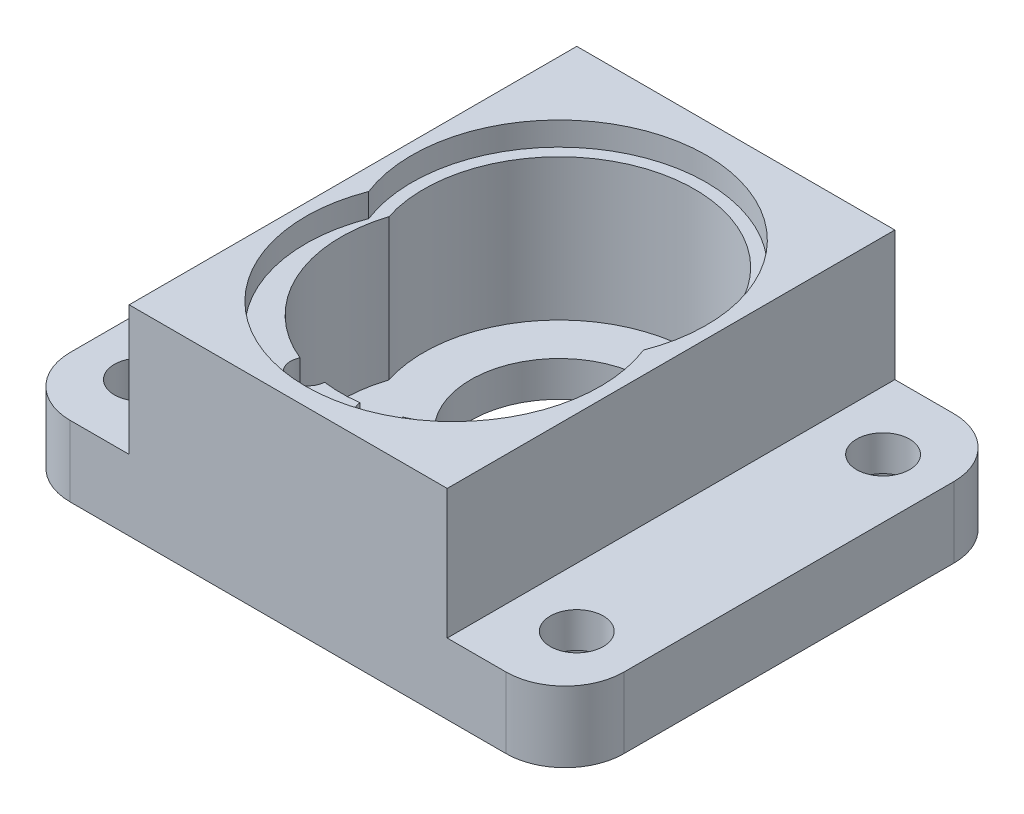
SolidWorks part; units mm, degrees
ref_plane "前视基准面" through (0, 0, 0) normal (0, 0, 1) x (1, 0, 0)
ref_plane "上视基准面" through (0, 0, 0) normal (0, 1, 0) x (1, 0, 0)
ref_plane "右视基准面" through (0, 0, 0) normal (1, 0, 0) x (0, 0, -1)
sketch "草图1" plane through (0, 0, 0) normal (0, 1, 0) x (1, 0, 0)
  line L0 (0, 0) -> (0, 23.6508) construction
  line L1 (-3, -10) -> (3, -10) construction
  line L2 (-9.5, 0) -> (9.5, 0) construction
  line L3 (0, 8.3) -> (0, -10) construction
  line L4 (0, 0) -> (10.4267, 0) construction
  line L5 (-13.5, 23.3) -> (-13.5, -14.7)
  line L6 (-13.5, 23.3) -> (13.5, 23.3)
  line L7 (0, 0.8) -> (1.4468, 0.8) construction
  line L8 (-13.5, -14.7) -> (13.5, -14.7)
  line L9 (0, -2) -> (1.3489, -2) construction
  line L10 (13.5, 23.3) -> (13.5, -14.7)
  circle A0 centre (0, 8.3) radius 7.5
  circle A1 centre (0, -5.5) radius 3.5
  circle A3 centre (-9.5, 0) radius 1.5
  circle A6 centre (-3, -10) radius 1.5
  circle A8 centre (9.5, 0) radius 1.5
  circle A9 centre (3, -10) radius 1.5
  dimension "D3" = 15
  dimension "D4" = 3
  dimension "D7" = 3
  dimension "D12" = 7
  dimension "D2" = 18.3
  dimension "D6" = 6
  dimension "D11" = 4.5
  dimension "D1" = 8.3
  dimension "D5" = 19
  dimension "D8" = 27
  dimension "D9" = 38
  dimension "D10" = 23
extrude "凸台-拉伸1" add sketch "草图1" along normal blind 3
sketch "草图4" plane through (0, 0, -23.3) normal (0, 0, -1) x (-1, 0, 0)
  line L0 (0, 0) -> (0, 15.4348) construction
  line L1 (-13.5, 0) -> (-23.5, 0)
  line L2 (-13.5, 0) -> (-13.5, 6)
  line L3 (-13.5, 6) -> (-23.5, 6)
  line L4 (-23.5, 0) -> (-23.5, 6)
  line L5 (13.5, 0) -> (23.5, 0)
  line L6 (13.5, 0) -> (13.5, 6)
  line L7 (23.5, 0) -> (23.5, 6)
  line L8 (13.5, 6) -> (23.5, 6)
  dimension "D1" = 10
  dimension "D2" = 6
extrude "凸台-拉伸3" add sketch "草图4" against normal up to surface (38 mm away) up to face at (0, 1.5, 14.7)
sketch "草图6" plane through (0, 0, 0) normal (0, -1, 0) x (1, 0, 0)
  circle A0 centre (-9.5, 0) radius 2.5
  circle A1 centre (9.5, 0) radius 2.5
  dimension "D1" = 5
  dimension "D2" = 5
extrude "切除-拉伸3" cut sketch "草图6" against normal blind 1
sketch "草图7" plane through (0, 3, 0) normal (0, 1, 0) x (1, 0, 0)
  line L0 (0, 23.3) -> (0, -14.7) construction
  line L1 (0, 0) -> (0, 24.4956) construction
  line L2 (0, 19.8) -> (8.5448, 19.8) construction
  line L3 (-10.9545, 4.8) -> (10.9545, 4.8) construction
  line L4 (0, -10.2) -> (9.1954, -10.2) construction
  line L5 (-13.5, 23.3) -> (13.5, 23.3)
  line L6 (-13.5, 23.3) -> (-13.5, -14.7)
  line L7 (-13.5, -14.7) -> (13.5, -14.7)
  line L8 (13.5, 23.3) -> (13.5, -14.7)
  line L9 (-13.5, -14.7) -> (13.5, -14.7) construction
  arc A1 (10.9545, 4.8) -> (-10.9545, 4.8) centre (0, 8.3) ccw
  arc A3 (-10.9545, 4.8) -> (10.9545, 4.8) centre (0, 1.3) ccw
  circle M1 centre (3, -10) radius 1.5
  circle M8 centre (-3, -10) radius 1.5
  dimension "D1" = 11.5
  dimension "D2" = 11.5
  dimension "D3" = 30
  dimension "D5" = 27
  dimension "D4" = 38
extrude "凸台-拉伸4" add sketch "草图7" along normal blind 14 contours A3 A1 M1 M8 region at (0, 3, -22.8338)
sketch "草图9" plane through (0, 3, 0) normal (0, 1, 0) x (1, 0, 0)
  line L0 (0, -13.2) -> (-15.6514, -13.2) construction
  line L1 (0, 20.8) -> (-29.1283, 20.8) construction
  arc A1 (11.6619, 3.8) -> (-11.6619, 3.8) centre (0, 8.3) ccw
  arc A2 (-11.6619, 3.8) -> (11.6619, 3.8) centre (0, -0.7) ccw
  dimension "D1" = 25
  dimension "D2" = 25
  dimension "D3" = 34
sketch "草图13" plane through (0, 6, 0) normal (0, 1, 0) x (1, 0, 0)
  line L0 (-18.5, 23.3) -> (-18.5, -14.7) construction
  line L1 (-23.5, 23.3) -> (-13.5, 23.3) construction
  line L2 (-13.5, -14.7) -> (-23.5, -14.7) construction
  line L3 (0, 23.3) -> (0, -14.7) construction
  line L5 (13.5, 23.3) -> (-13.5, 23.3) construction
  line L6 (-13.5, -14.7) -> (13.5, -14.7) construction
  circle A0 centre (-18.5, 17.3) radius 2.25
  circle A1 centre (-18.5, -8.7) radius 2.25
  circle A2 centre (18.5, -8.7) radius 2.25
  circle A3 centre (18.5, 17.3) radius 2.25
  dimension "D3" = 4.5
  dimension "D4" = 4.5
  dimension "D1" = 6
  dimension "D2" = 6
extrude "切除-拉伸6" cut sketch "草图13" against normal blind 10
sketch "草图15" plane through (0, 17, 0) normal (0, 1, 0) x (1, 0, 0)
  arc A2 (11.6619, 3.8) -> (-11.6619, 3.8) centre (0, 8.3) ccw
  arc A3 (-11.6619, 3.8) -> (11.6619, 3.8) centre (0, -0.7) ccw
  arc A4 (11.6619, 3.8) -> (-11.6619, 3.8) centre (0, 8.3) ccw
  arc A5 (-11.6619, 3.8) -> (11.6619, 3.8) centre (0, -0.7) ccw
  dimension "D1" = 0
extrude "切除-拉伸8" cut sketch "草图15" against normal blind 2
fillet "圆角1" radius 5 4 edges at (23.5, 3, -23.3) (23.5, 3, 14.7) (-23.5, 3, 14.7) (-23.5, 3, -23.3)
ref_plane "基准面1" through (0, 9, 0) normal (0, 1, 0) x (1, 0, 0)
sketch "草图16" plane through (0, 9, 0) normal (0, 1, 0) x (1, 0, 0)
  line L0 (-11.5657, -10.3164) -> (0, 0) construction
  line L1 (0, 0) -> (0, -13.2) construction
  line L2 (11.5657, -10.3164) -> (0, 0) construction
  arc A0 (-11.6619, 3.8) -> (11.6619, 3.8) centre (0, -0.7) ccw construction
sketch "草图17" plane through (0, 0, 0) normal (0, -1, 0) x (1, 0, 0)
  circle A0 centre (-18.5, 8.7) radius 4
  circle A1 centre (18.5, 8.7) radius 4
  circle A2 centre (18.5, -17.3) radius 4
  circle A3 centre (-18.5, -17.3) radius 4
  dimension "D1" = 8
extrude "切除-拉伸9" cut sketch "草图17" against normal blind 3
